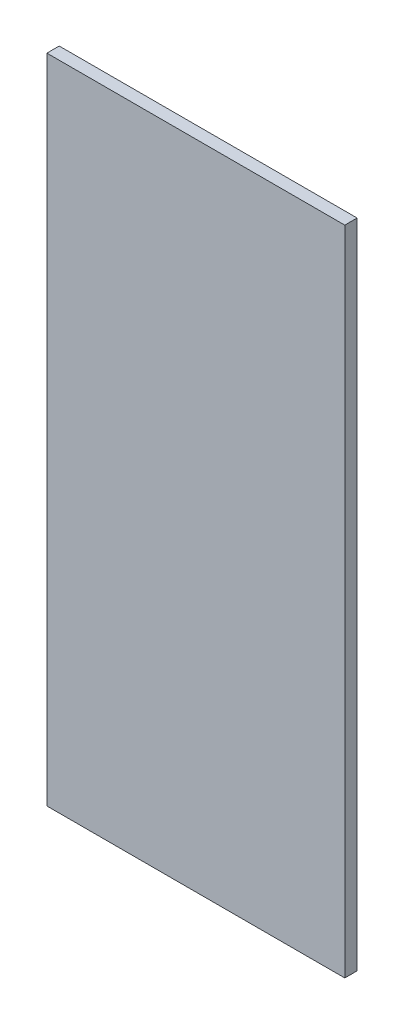
SolidWorks part; units mm, degrees
material "Perspex (TM) GS Acrylic Cast Sheet"
ref_plane "Front Plane" through (0, 0, 0) normal (0, 0, 1) x (1, 0, 0)
ref_plane "Top Plane" through (0, 0, 0) normal (0, 1, 0) x (1, 0, 0)
ref_plane "Right Plane" through (0, 0, 0) normal (1, 0, 0) x (0, 0, -1)
sketch "Sketch1" plane through (0, 0, 0) normal (0, 0, 1) x (1, 0, 0)
  line L1 (-72.5, -158.685) -> (72.5, -158.685)
  line L2 (-72.5, -158.685) -> (-72.5, 158.685)
  line L3 (-72.5, 158.685) -> (72.5, 158.685)
  line L4 (72.5, -158.685) -> (72.5, 158.685)
  line L5 (-72.5, -158.685) -> (72.5, 158.685) construction
  line L6 (-72.5, 158.685) -> (72.5, -158.685) construction
  point P0 (0, 0)
  dimension "D1" = 145
  dimension "D2" = 317.37
extrude "Boss-Extrude1" add sketch "Sketch1" along normal blind 6
equation "\"PCLength\"= 145mm'Length across I/O from PS to GPU"
equation "\"PCWidth\"= 340mm'Distance of longest part parallel to GPU(ussually GPU)"
equation "\"PCHeight\"= 180mm'Tallest point with mobo laying flat"
equation "\"WallThickness\"= 9mm'Thickness of each outer tank wall"
equation "\"ThermoBarrierThickness\"= 6mm'Thickness of barrier between hot side and cold side"
equation "\"HotSideGap\"= 36mm'Space in the hot side for a pump"
equation "\"PCClearance\"= 40mm'Clearance from top of tank to top of PC"
equation "\"RadiatorHeight\"= 277.37mm'Final Height from ground of radiators"
equation "\"D1@Sketch1\"=\"PCLength\""
equation "\"D2@Sketch1\"=\"RadiatorHeight\" + 40"
equation "\"D1@Boss-Extrude1\"=\"ThermoBarrierThickness\""
